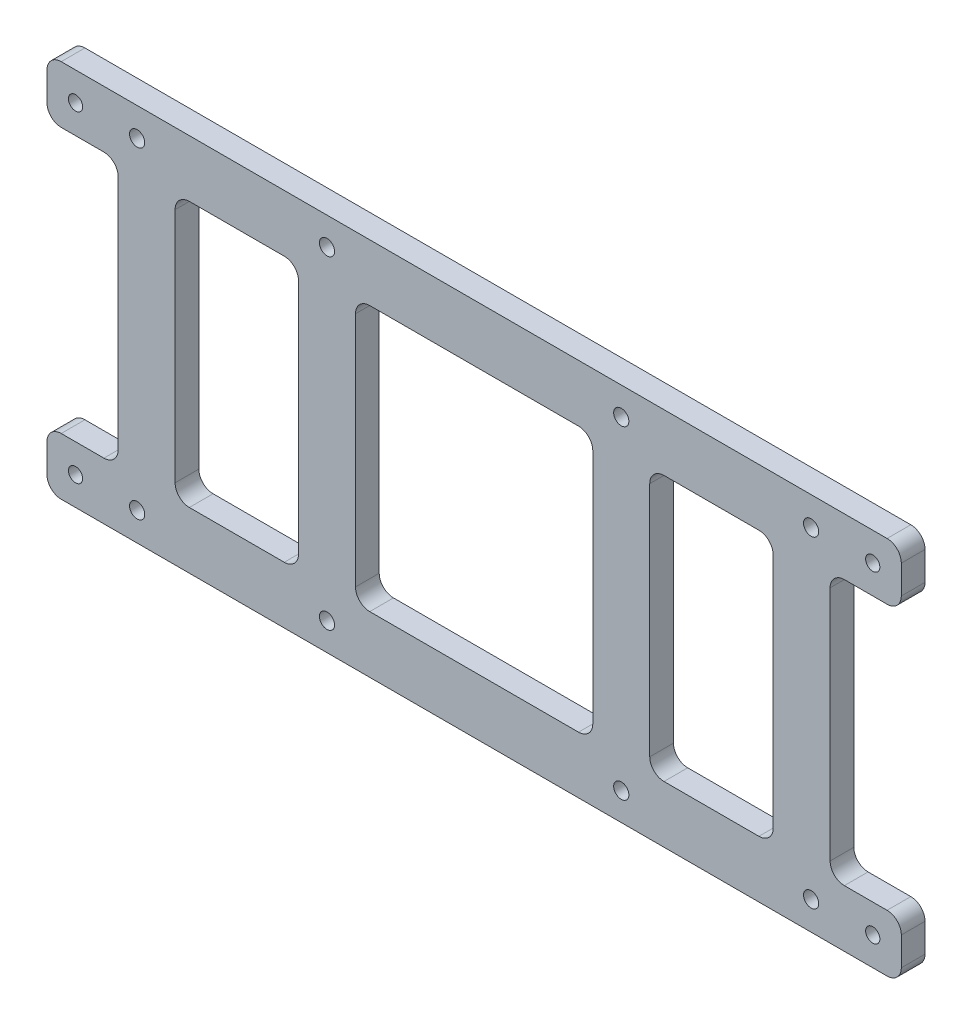
SolidWorks part; units mm, degrees
material "Thornel Mat VMA"
ref_plane "前视基准面" through (0, 0, 0) normal (0, 0, 1) x (1, 0, 0)
ref_plane "上视基准面" through (0, 0, 0) normal (0, 1, 0) x (1, 0, 0)
ref_plane "右视基准面" through (0, 0, 0) normal (1, 0, 0) x (0, 0, -1)
sketch "草图1" plane through (0, 0, 0) normal (0, 0, 1) x (1, 0, 0)
  line L0 (-8, 27.8432) -> (-8, -28)
  line L2 (-8, 40) -> (-8, 39.8432)
  line L4 (142, 40) -> (142, 39.8432)
  line L5 (-20, 39.8432) -> (154, 39.8432)
  line L6 (-23, 36.8432) -> (-23, 30.8432)
  line L7 (-20, 27.8432) -> (-8, 27.8432)
  line L8 (157, 36.8432) -> (157, 30.8432)
  line L9 (-20, -40) -> (154, -40)
  line L10 (-23, -37) -> (-23, -31)
  line L11 (-20, -28) -> (-8, -28)
  line L12 (157, -37) -> (157, -31)
  line L13 (142, 27.8432) -> (154, 27.8432)
  line L14 (142, -28) -> (154, -28)
  line L15 (142, 27.8432) -> (142, -28)
  line L17 (7, 27.8432) -> (127, 27.8432)
  line L18 (4, 24.8432) -> (4, -25)
  line L19 (7, -28) -> (127, -28)
  line L20 (130, 24.8432) -> (130, -25)
  arc A0 (154, -40) -> (157, -37) centre (154, -37) ccw
  arc A1 (154, -28) -> (157, -31) centre (154, -31) cw
  arc A2 (154, 27.8432) -> (157, 30.8432) centre (154, 30.8432) ccw
  arc A3 (154, 39.8432) -> (157, 36.8432) centre (154, 36.8432) cw
  arc A4 (-20, -40) -> (-23, -37) centre (-20, -37) cw
  arc A5 (-23, -31) -> (-20, -28) centre (-20, -31) cw
  arc A6 (-23, 30.8432) -> (-20, 27.8432) centre (-20, 30.8432) ccw
  arc A7 (-20, 39.8432) -> (-23, 36.8432) centre (-20, 36.8432) ccw
  arc A8 (127, -28) -> (130, -25) centre (127, -25) ccw
  arc A9 (127, 27.8432) -> (130, 24.8432) centre (127, 24.8432) cw
  arc A10 (4, -25) -> (7, -28) centre (7, -25) ccw
  arc A11 (7, 27.8432) -> (4, 24.8432) centre (7, 24.8432) ccw
  point P20 (157, -40)
  point P23 (157, -28)
  point P26 (157, 27.8432)
  point P29 (157, 39.8432)
  dimension "D7" = 3
  dimension "D10" = 3
  dimension "D1" = 15
  dimension "D2" = 15
  dimension "D3" = 15
  dimension "D4" = 15
  dimension "D5" = 12
  dimension "D6" = 12
  dimension "D8" = 12
  dimension "D9" = 12
  dimension "D11" = 150
extrude "凸台-拉伸1" add sketch "草图1" along normal blind 5 contours L5 A7 L6 A6 L7 L0 L11 A5 L10 A4 L9 A0 L12 A1 L14 L15 L13 A2 L8 A3 A11 L17 A9 L20 A8 L19 A10 L18 region at (-14, 29.8124, 0)
fillet "圆角1" radius 3 4 edges at (-8, -28, 2.5) (-8, 27.8432, 2.5) (142, -28, 2.5) (142, 27.8432, 2.5)
sketch "草图2" plane through (0, 0, 5) normal (0, 0, 1) x (1, 0, 0)
  line L0 (67, 39.8432) -> (67, -40) construction
  line L1 (-20, 39.8432) -> (154, 39.8432) construction
  line L2 (-20, -40) -> (154, -40) construction
  line L3 (-8, -0.0784) -> (142, -0.0784) construction
  line L4 (-8, 24.8432) -> (-8, -25) construction
  line L5 (142, 24.8432) -> (142, -25) construction
  line L6 (32.0016, 40) -> (40.0016, 40) construction
  line L7 (32.0016, -40) -> (32.0016, -25) construction
  circle A0 centre (-16.978, 33.8432) radius 1.5
  circle A1 centre (-4, 33.8432) radius 1.6
  circle A2 centre (36.0016, 34) radius 1.6
  circle A3 centre (97.9984, 34) radius 1.6
  circle A4 centre (138, 33.8432) radius 1.6
  circle A5 centre (150.978, 33.8432) radius 1.5
  circle A6 centre (150.978, -34) radius 1.5
  circle A7 centre (138, -34) radius 1.6
  circle A8 centre (97.9984, -34.1568) radius 1.6
  circle A9 centre (36.0016, -34.1568) radius 1.6
  circle A10 centre (-4, -34) radius 1.6
  circle A11 centre (-16.978, -34) radius 1.5
  dimension "D1" = 3
  dimension "D2" = 3.2
  dimension "D3" = 3.2
  dimension "D4" = 6
  dimension "D5" = 6
  dimension "D6" = 6
  dimension "D7" = 4
  dimension "D8" = 4
extrude "切除-拉伸1" cut sketch "草图2" against normal blind 7
sketch "草图3" plane through (0, 0, 0) normal (0, 0, -1) x (-1, 0, 0)
  line L0 (-7, 27.8432) -> (-127, 27.8432) construction
  line L1 (-103.9984, 27.8432) -> (-91.9984, 27.8432)
  line L2 (-103.9984, 27.8432) -> (-103.9984, -28)
  line L3 (-103.9984, -28) -> (-91.9984, -28)
  line L4 (-91.9984, 27.8432) -> (-91.9984, -28)
  line L5 (-7, -28) -> (-127, -28) construction
  line L6 (-40.0016, 40) -> (-40.0016, 25) construction
  line L7 (-42.0016, 27.8432) -> (-30.0016, 27.8432)
  line L8 (-42.0016, 27.8432) -> (-42.0016, -28)
  line L9 (-42.0016, -28) -> (-30.0016, -28)
  line L10 (-30.0016, 27.8432) -> (-30.0016, -28)
  line L11 (-101.9984, -40) -> (-101.9984, -25) construction
  dimension "D1" = 12
  dimension "D2" = 12
  dimension "D3" = 2
  dimension "D4" = 2
extrude "凸台-拉伸2" add sketch "草图3" against normal blind 5
fillet "圆角2" radius 3 8 edges at (42.0016, 27.8432, 2.5) (42.0016, -28, 2.5) (91.9984, -28, 2.5) (30.0016, -28, 2.5) (30.0016, 27.8432, 2.5) (91.9984, 27.8432, 2.5) (103.9984, -28, 2.5) (103.9984, 27.8432, 2.5)
